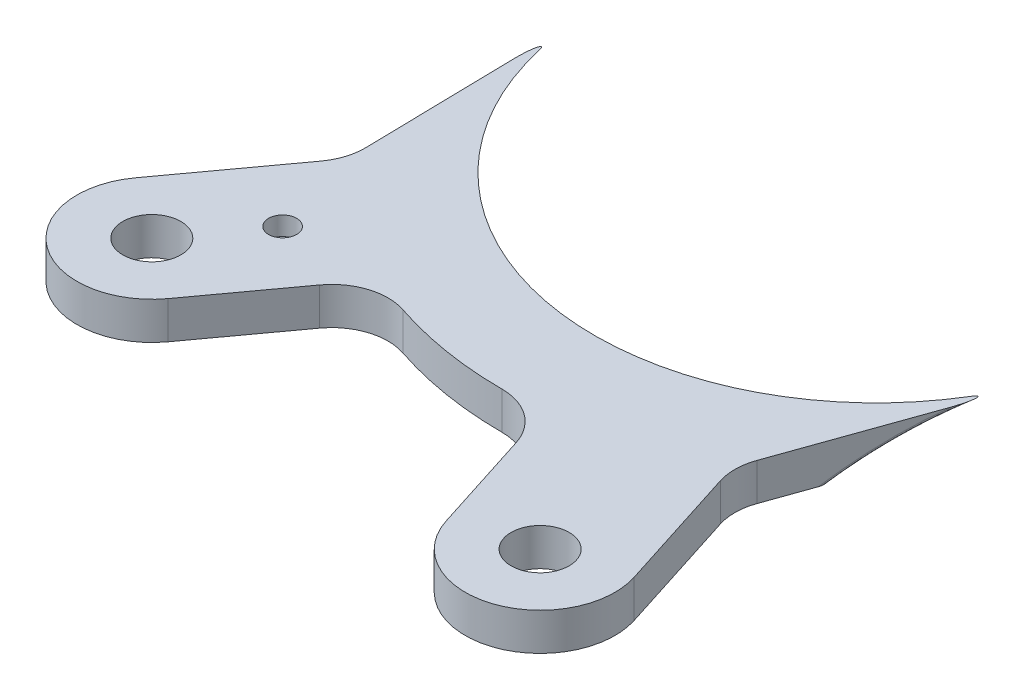
SolidWorks part; units mm, degrees
note: '?' marks a value the reader was unsure of.
ref_plane "前视基准面" through (0, 0, 0) normal (0, 0, 1) x (1, 0, 0)
ref_plane "上视基准面" through (0, 0, 0) normal (0, 1, 0) x (1, 0, 0)
ref_plane "右视基准面" through (0, 0, 0) normal (1, 0, 0) x (0, 0, -1)
other "Configuration Table"
sketch "草图1" plane through (0, 0, 0) normal (0, 1, 0) x (1, 0, 0)
  line L0 (-9.4276, 12.118) -> (-14.206, 5.5725)
  line L1 (-7.7445, 0.8555) -> (-2.9662, 7.401)
  line L2 (5.3573, 25.5867) -> (-10.9753, 3.214)
  line L3 (9.974, -2.0172) -> (7.5085, 5.7028)
  line L4 (17.5948, 0.4166) -> (15.1293, 8.1366)
  line L5 (13.7844, -0.8003) -> (5.3573, 25.5867)
  line L6 (15.1293, 8.1366) -> (19.5389, 20.5484)
  line L7 (-9.4276, 12.118) -> (-9.6898, 25.2872)
  circle A0 centre (-10.9753, 3.214) radius 1.55
  circle A1 centre (13.7844, -0.8003) radius 1.55
  circle A2 centre (5.3573, 25.5867) radius 15.05
  circle A3 centre (-10.9753, 3.214) radius 4
  circle A4 centre (13.7844, -0.8003) radius 4
  circle A5 centre (5.3573, 25.5867) radius 20
  dimension "D1" = 3.1
  dimension "D2" = 3.1
  dimension "D3" = 30.1
  dimension "D4" = 40
  dimension "D5" = 8
extrude "凸台-拉伸1" add sketch "草图1" along normal blind 2
fillet "圆角1" radius 3 4 edges at (-9.4276, 1, -12.118) (15.1293, 1, -8.1366) (7.5085, 1, -5.7028) (-2.9662, 1, -7.401)
ref_axis "基准轴1" through (5.3573, 2, -25.5867) along (0, -1, 0)?
ref_plane "基准面1" through (5.3573, 0, 0) normal (-1, 0, 0) x (0, -1, 0)
sketch "草图2" plane through (5.3573, 0, 0) normal (-1, 0, 0) x (0, -1, 0)
  line L0 (-2, -10.5367) -> (-2, -25.2872) construction
  line L1 (-2, -10.5367) -> (-2, -25.5867) construction
  line L2 (-2, -25.5867) -> (0, -25.5867) construction
  line L3 (43.03, -25.5867) -> (-7.03, -25.5867)
  arc A0 (43.03, -25.5867) -> (-7.03, -25.5867) centre (18, -25.5867) ccw
  dimension "D2" = 15.05
  dimension "D1" = 20
revolve "切除-旋转1" cut sketch "草图2" angle 360 about L3
fillet "圆角2" radius 0.2 2 edges at (-9.6008, 1.4936, -20.816) (18.0417, 1.4936, -16.3343)
sketch "草图3" plane through (0, 2, 0) normal (0, 1, 0) x (1, 0, 0)
  line L0 (-10.9753, 3.214) -> (-8.0271, 7.2524) construction
  line L1 (-7.7445, 0.8555) -> (-4.33, 5.5329) construction
  circle A0 centre (-8.0271, 7.2524) radius 0.75
  dimension "D2" = 1.5
  dimension "D1" = 5
extrude "切除-拉伸1" cut sketch "草图3" against normal blind 1
